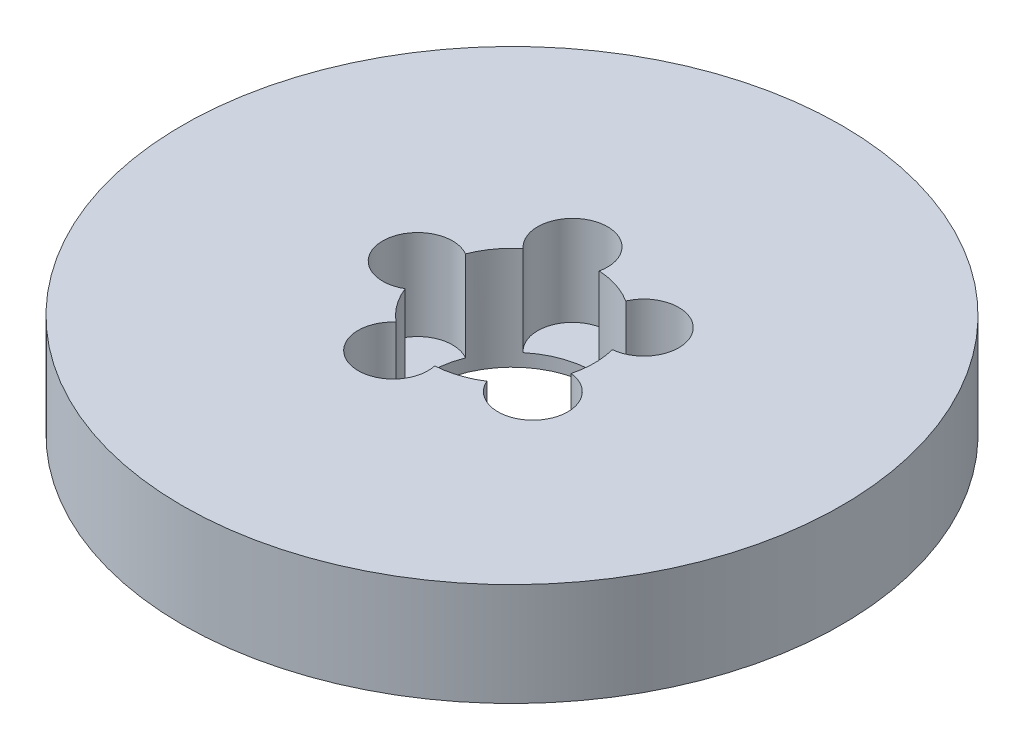
SolidWorks part; units mm, degrees
ref_plane "Front Plane" through (0, 0, 0) normal (0, 0, 1) x (1, 0, 0)
ref_plane "Top Plane" through (0, 0, 0) normal (0, 1, 0) x (1, 0, 0)
ref_plane "Right Plane" through (0, 0, 0) normal (1, 0, 0) x (0, 0, -1)
sketch "Sketch1" plane through (0, 0, 0) normal (0, 1, 0) x (1, 0, 0)
  circle A0 centre (0, 0) radius 80
  dimension "FLANGE_OD" = 160
extrude "Boss-Extrude1" add sketch "Sketch1" along normal blind 25
sketch "Sketch2" plane through (0, 0, 0) normal (0, 1, 0) x (1, 0, 0)
  circle A0 centre (0, 0) radius 20
  dimension "BORE_D" = 40
extrude "Cut-Extrude1" cut sketch "Sketch2" along normal through all
sketch "Sketch3" plane through (0, 25, 0) normal (0, 1, 0) x (1, 0, 0)
  circle A0 centre (0, 0) radius 22.9072 construction
  circle A1 centre (-22.9072, 0) radius 8.4892
  dimension "BOLT_D" = 16.9784
  dimension "BOLT_PCD" = 45.8143
extrude "Cut-Extrude2" cut sketch "Sketch3" against normal blind 21.8704
pattern_circular "CirPattern1" count 5 over 360 about axis through (0, 0, 0) along (0, 1, 0) of "Cut-Extrude2"
